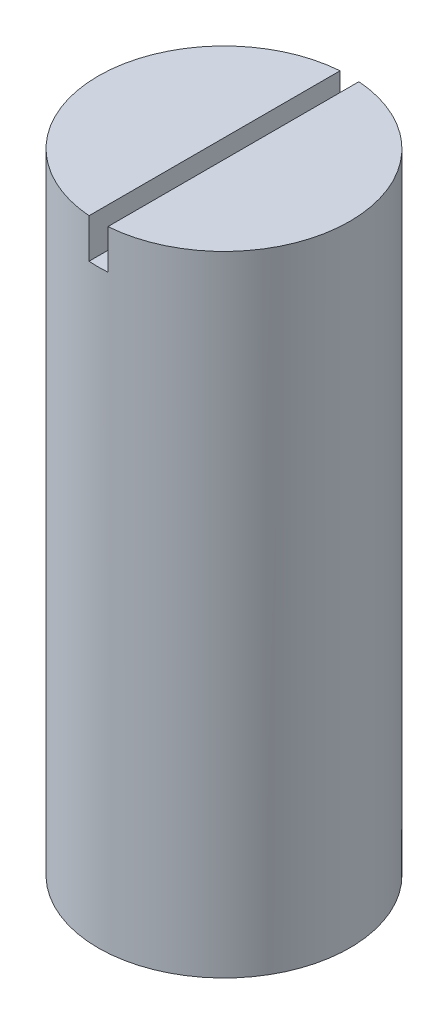
SolidWorks part; units mm, degrees
material "Gray Cast Iron"
ref_plane "Front Plane" through (0, 0, 0) normal (0, 0, 1) x (1, 0, 0)
ref_plane "Top Plane" through (0, 0, 0) normal (0, 1, 0) x (1, 0, 0)
ref_plane "Right Plane" through (0, 0, 0) normal (1, 0, 0) x (0, 0, -1)
sketch "Sketch1" plane through (0, 0, 0) normal (0, 1, 0) x (1, 0, 0)
  circle A0 centre (0, 0) radius 16
  dimension "D1" = 32
extrude "Boss-Extrude1" add sketch "Sketch1" along normal blind 80
sketch "Sketch2" plane through (0, 0, 0) normal (0, 0, 1) x (1, 0, 0)
  line L0 (-1.2, 74.984) -> (1.2, 74.984)
  line L1 (1.2, 74.984) -> (1.2, 82)
  line L2 (1.2, 82) -> (-1.2, 82)
  line L3 (-1.2, 82) -> (-1.2, 74.984)
extrude "Cut-Extrude1" cut sketch "Sketch2" against normal mid plane 36
